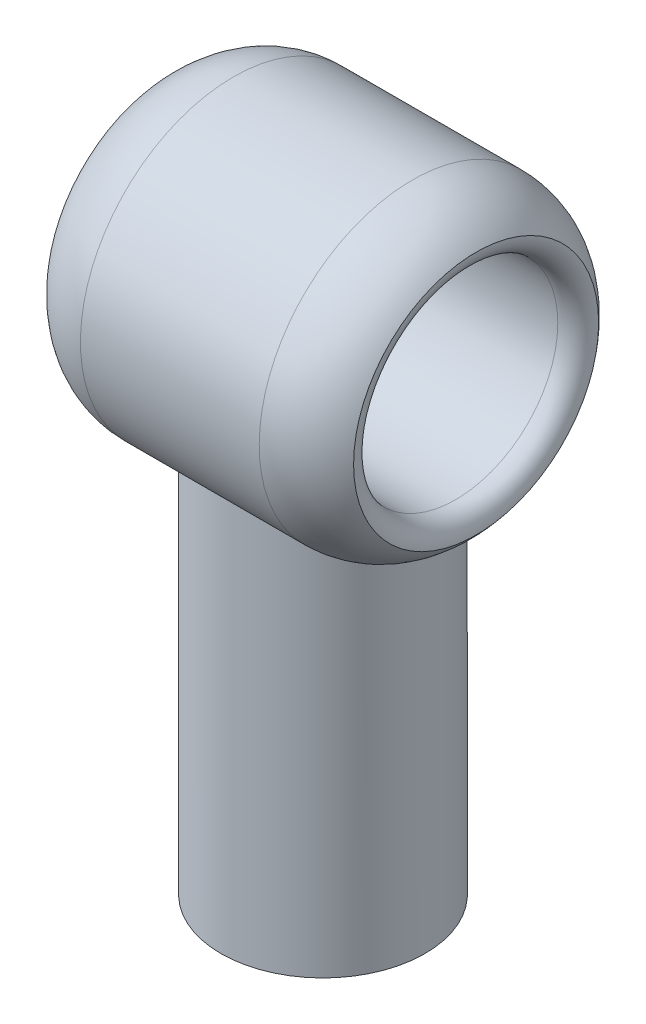
SolidWorks part; units mm, degrees
ref_plane "Plan de face" through (0, 0, 0) normal (0, 0, 1) x (1, 0, 0)
ref_plane "Plan de dessus" through (0, 0, 0) normal (0, 1, 0) x (1, 0, 0)
ref_plane "Plan de droite" through (0, 0, 0) normal (1, 0, 0) x (0, 0, -1)
sketch "Esquisse2" plane through (0, 0, 0) normal (0, 1, 0) x (1, 0, 0)
  circle A0 centre (0, 0) radius 10
  dimension "D1" = 20
extrude "Boss.-Extru.2" add sketch "Esquisse2" along normal blind 40
sketch "Esquisse3" plane through (0, 0, 0) normal (0, -1, 0) x (1, 0, 0)
  circle A0 centre (0, 0) radius 7.25
  dimension "D1" = 14.5
extrude "Enlèv. mat.-Extru.1" cut sketch "Esquisse3" against normal blind 30
cosmetic thread "Représentation de filetage1" parameters "D2"=16
cosmetic thread "Représentation de filetage2" parameters "D2"=16
cosmetic thread "Représentation de filetage3" parameters "D2"=16
cosmetic thread "Représentation de filetage4" parameters "D2"=16
fillet "Congé2" radius 2 1 edges at (0, 30, -7.25)
sketch "Esquisse9" plane through (0, 0, 0) normal (1, 0, 0) x (0, 0, -1)
  line L0 (0, -1000) -> (0, 49000) construction
  line L1 (-10, 0) -> (10, 0) construction
  circle A0 centre (0, 50) radius 15
  dimension "D1" = 30
  dimension "D2" = 50
extrude "Boss.-Extru.3" add sketch "Esquisse9" along normal mid plane 30 contours A0
sketch "Esquisse10" plane through (15, 0, 0) normal (1, 0, 0) x (0, 0, -1)
  circle A0 centre (0, 50) radius 10
extrude "Enlèv. mat.-Extru.2" cut sketch "Esquisse10" against normal blind 30
fillet "Congé3" radius 2 1 edges at (15, 50, -10)
fillet "Congé4" radius 2 1 edges at (-15, 50, -10)
fillet "Congé5" radius 8 1 edges at (15, 50, -15)
fillet "Congé6" radius 8 1 edges at (-15, 50, -15)
